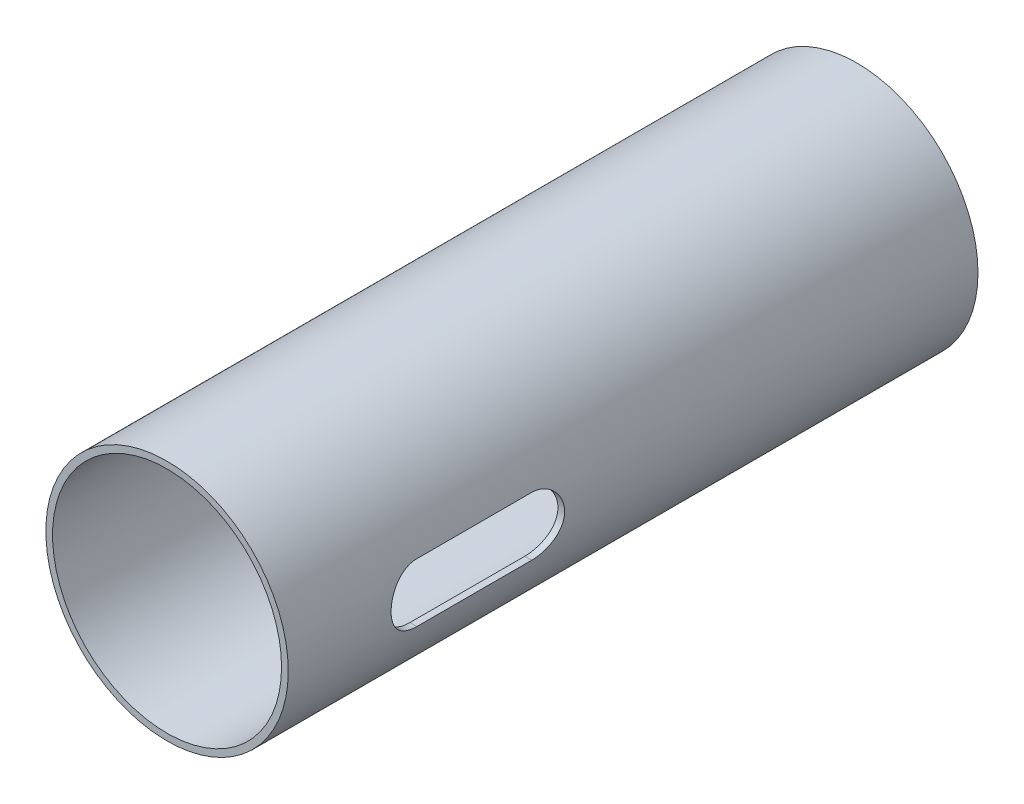
SolidWorks part; units mm, degrees
material "3003 Alloy"
ref_plane "Front Plane" through (0, 0, 0) normal (0, 0, 1) x (1, 0, 0)
ref_plane "Top Plane" through (0, 0, 0) normal (0, 1, 0) x (1, 0, 0)
ref_plane "Right Plane" through (0, 0, 0) normal (1, 0, 0) x (0, 0, -1)
sketch "Sketch1" plane through (0, 0, 0) normal (0, 0, 1) x (1, 0, 0)
  circle A0 centre (-89.675, 9.5336) radius 12.6309
extrude "Boss-Extrude1" add sketch "Sketch1" along normal blind 71.882
shell "Shell1" thickness 0.6985 removed face at (-77.0441, 9.5336, 0) removed face at (-77.0441, 9.5336, 71.882)
ref_plane "Plane1" through (-89.662, 0, 0) normal (1, 0, 0) x (0, 0, -1)
sketch "Sketch4" plane through (-89.662, 0, 0) normal (1, 0, 0) x (0, 0, -1)
  line L3 (-58.1025, 12.5943) -> (-46.1391, 12.5943)
  line L4 (-58.1025, 6.4729) -> (-46.1391, 6.4729)
  arc A0 (-58.1025, 12.5943) -> (-58.1025, 6.4729) centre (-58.1025, 9.5336) ccw
  arc A1 (-46.1391, 6.4729) -> (-46.1391, 12.5943) centre (-46.1391, 9.5336) ccw
extrude "Cut-Extrude1" cut sketch "Sketch4" along normal blind 71.882
